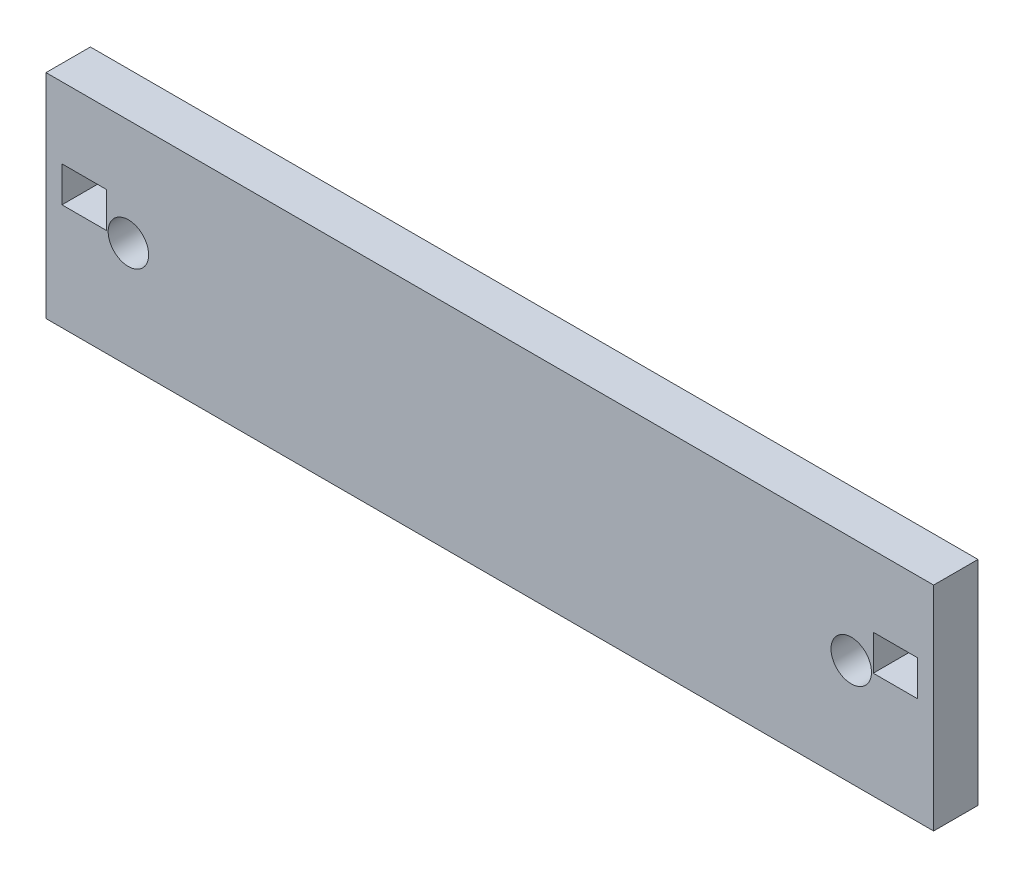
SolidWorks part; units mm, degrees
material "Beech"
ref_plane "Front Plane" through (0, 0, 0) normal (0, 0, 1) x (1, 0, 0)
ref_plane "Top Plane" through (0, 0, 0) normal (0, 1, 0) x (1, 0, 0)
ref_plane "Right Plane" through (0, 0, 0) normal (1, 0, 0) x (0, 0, -1)
sketch "Sketch1" plane through (0, 0, 0) normal (0, 0, 1) x (1, 0, 0)
  line L0 (0, -1000) -> (0, 49000) construction
  line L1 (-15.875, -3.81) -> (15.875, -3.81)
  line L2 (-15.875, -3.81) -> (-15.875, 3.81)
  line L3 (-15.875, 3.81) -> (15.875, 3.81)
  line L4 (15.875, -3.81) -> (15.875, 3.81)
  line L5 (-15.875, -3.81) -> (15.875, 3.81) construction
  line L6 (-15.875, 3.81) -> (15.875, -3.81) construction
  line L7 (-15.3035, 0) -> (-13.716, 0)
  line L8 (-15.3035, 0) -> (-15.3035, 1.27)
  line L9 (-15.3035, 1.27) -> (-13.716, 1.27)
  line L10 (-13.716, 0) -> (-13.716, 1.27)
  line L11 (13.716, 0) -> (13.716, 1.27)
  line L12 (15.3035, 1.27) -> (13.716, 1.27)
  line L13 (15.3035, 0) -> (15.3035, 1.27)
  line L14 (15.3035, 0) -> (13.716, 0)
  line L15 (-1000, 0) -> (49000, 0) construction
  circle A0 centre (-12.9286, 0) radius 0.7239
  circle A1 centre (12.9286, 0) radius 0.7239
  point P0 (0, 0)
  dimension "D6" = 1.4478
  dimension "D7" = 0.7874
  dimension "D1" = 31.75
  dimension "D2" = 7.62
  dimension "D3" = 1.5875
  dimension "D4" = 13.716
  dimension "D5" = 1.27
extrude "Boss-Extrude1" add sketch "Sketch1" along normal blind 1.5875
